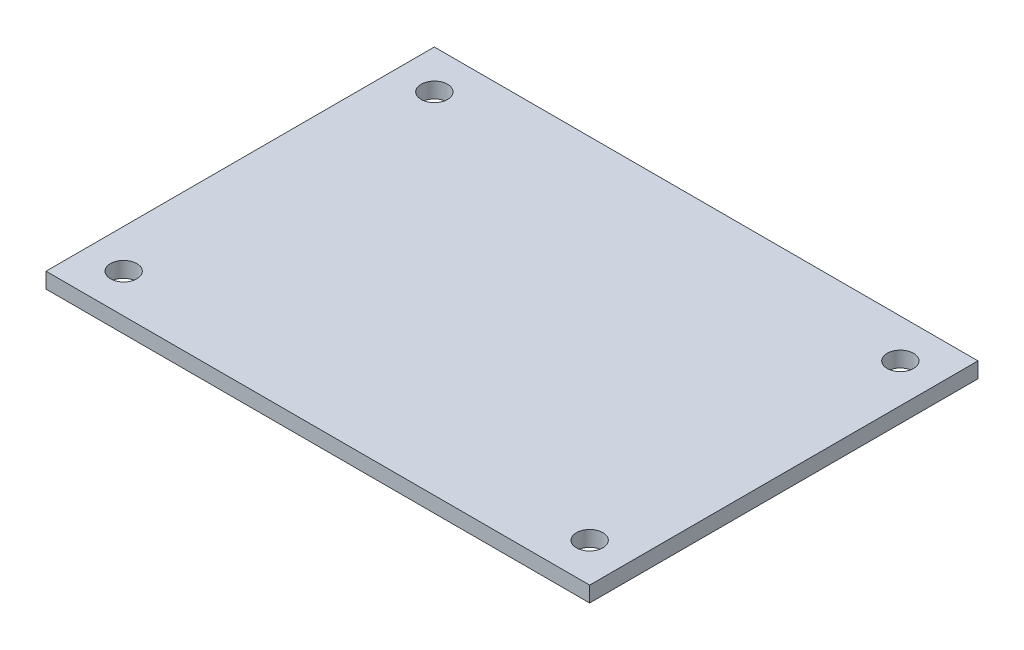
SolidWorks part; units mm, degrees
ref_plane "Front Plane" through (0, 0, 0) normal (0, 0, 1) x (1, 0, 0)
ref_plane "Top Plane" through (0, 0, 0) normal (0, 1, 0) x (1, 0, 0)
ref_plane "Right Plane" through (0, 0, 0) normal (1, 0, 0) x (0, 0, -1)
sketch "Sketch1" plane through (0, 0, 0) normal (0, 1, 0) x (1, 0, 0)
  line L1 (-35, 25) -> (35, 25)
  line L2 (-35, 25) -> (-35, -25)
  line L3 (-35, -25) -> (35, -25)
  line L4 (35, 25) -> (35, -25)
  line L5 (-35, 25) -> (35, -25) construction
  line L6 (-35, -25) -> (35, 25) construction
  circle A0 centre (-30, 20) radius 1.7
  circle A1 centre (30, 20) radius 1.7
  circle A2 centre (30, -20) radius 1.7
  circle A3 centre (-30, -20) radius 1.7
  point P0 (0, 0)
  point P14 (0, 0)
  point P15 (0, 0)
  point P16 (0, 0)
  point P17 (0, 0)
  point P18 (0, 0)
  dimension "D1" = 40
  dimension "D2" = 60
  dimension "D3" = 20
  dimension "D4" = 30
  dimension "D5" = 3.4
  dimension "D6" = 5
  dimension "D7" = 5
extrude "Boss-Extrude1" add sketch "Sketch1" along normal blind 2
